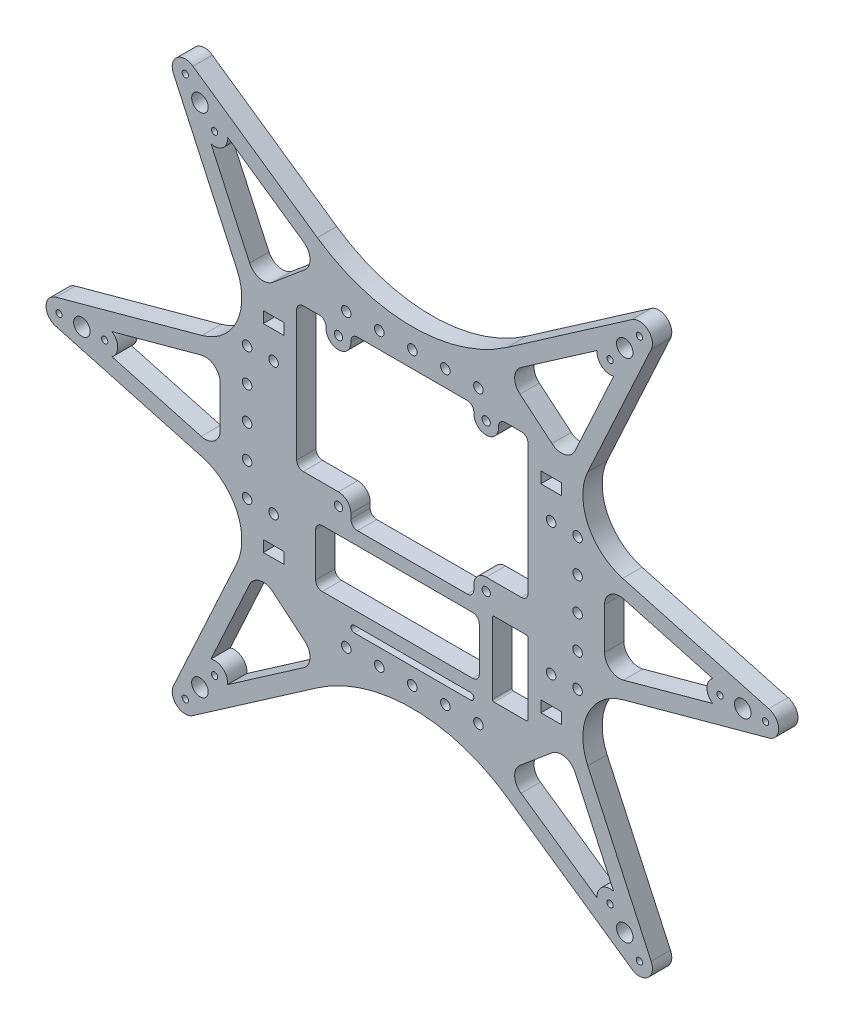
SolidWorks part; units mm, degrees
material "Acrylic (Medium-high impact)"
ref_plane "Front Plane" through (0, 0, 0) normal (0, 0, 1) x (1, 0, 0)
ref_plane "Top Plane" through (0, 0, 0) normal (0, 1, 0) x (1, 0, 0)
ref_plane "Right Plane" through (0, 0, 0) normal (1, 0, 0) x (0, 0, -1)
sketch "Sketch1" plane through (0, 0, 0) normal (0, 0, 1) x (1, 0, 0)
  line L0 (587.1768, 489.0962) -> (587.1768, 412.0041) construction
  line L1 (549.3782, 453.8298) -> (576.3894, 461.205)
  line L2 (582.1207, 456.8289) -> (582.1207, 444.2715)
  line L3 (595.1767, 418.8502) -> (601.3767, 422.2502) construction
  line L4 (595.1767, 422.2502) -> (601.3767, 418.8502) construction
  line L5 (568.9811, 379.8335) -> (581.557, 369.2811) construction
  line L6 (640.2767, 406.5502) -> (630.2767, 406.5502) construction
  line L7 (590.2767, 450.5502) -> (590.2767, 440.5502) construction
  line L8 (-358.708, 400.5502) -> (49641.292, 400.5502) construction
  line L9 (532.4267, 446.7161) -> (532.4267, 454.3842) construction
  line L10 (640.2767, 450.5502) -> (-31503.6634, -37857.1058) construction
  line L11 (704.5554, 373.9457) -> (708.9906, 368.66) construction
  line L12 (704.5554, 373.9457) -> (700.1202, 379.2314) construction
  line L13 (709.6013, 367.9323) -> (706.6642, 365.4678) construction
  line L14 (575.9979, 527.1546) -> (571.5627, 532.4403) construction
  line L15 (575.9979, 527.1546) -> (580.4331, 521.8689) construction
  line L16 (712.5384, 370.3968) -> (709.6013, 367.9323) construction
  line L17 (576.6167, 466.4501) -> (576.6167, 434.6502) construction
  line L18 (663.4579, 422.9239) -> (640.2767, 450.5502) construction
  line L19 (570.952, 533.1681) -> (573.8891, 535.6326) construction
  line L20 (568.0149, 370.3968) -> (570.952, 367.9323) construction
  line L21 (540.2767, 450.5502) -> (547.1767, 450.5502) construction
  line L22 (-351.1587, 450.5502) -> (49648.8413, 450.5502) construction
  line L23 (685.3767, 422.2502) -> (679.1767, 418.8502) construction
  line L24 (685.3767, 418.8502) -> (679.1767, 422.2502) construction
  line L25 (685.3767, 482.2502) -> (679.1767, 478.8502) construction
  line L26 (587.1768, 489.0962) -> (568.0149, 530.7036)
  line L27 (570.952, 367.9323) -> (573.8891, 365.4678) construction
  line L28 (575.9979, 373.9457) -> (580.4331, 379.2314) construction
  line L29 (685.3767, 478.8502) -> (679.1767, 482.2502) construction
  line L30 (611.5369, 509.5368) -> (573.8891, 535.6326)
  line L31 (568.0149, 530.7036) -> (570.952, 533.1681) construction
  line L32 (610.8062, 450.5502) -> (605.2767, 450.5502) construction
  line L33 (605.2767, 489.5502) -> (675.2767, 489.5502)
  line L34 (663.4579, 478.1765) -> (640.2767, 450.5502) construction
  line L35 (540.2767, 450.5502) -> (533.3767, 450.5502) construction
  line L36 (576.6167, 466.4501) -> (532.4267, 454.3842)
  line L37 (575.9979, 373.9457) -> (571.5627, 368.66) construction
  line L38 (595.1767, 422.2502) -> (595.1767, 418.8502)
  line L39 (595.1767, 422.2502) -> (601.3767, 422.2502)
  line L40 (601.3767, 422.2502) -> (601.3767, 418.8502)
  line L41 (640.2767, 450.5502) -> (675.2767, 450.5502) construction
  line L42 (595.1767, 418.8502) -> (601.3767, 418.8502)
  line L43 (731.1751, 447.2706) -> (704.1639, 439.8953)
  line L44 (685.3767, 418.8502) -> (679.1767, 418.8502)
  line L45 (740.2767, 450.5502) -> (747.1767, 450.5502) construction
  line L46 (693.3765, 412.0041) -> (712.5384, 370.3968)
  line L47 (669.7471, 450.5502) -> (675.2767, 450.5502) construction
  line L48 (669.0164, 391.5635) -> (706.6642, 365.4678)
  line L49 (703.9366, 434.6502) -> (748.1267, 446.7161)
  line L50 (712.5384, 530.7036) -> (709.6013, 533.1681) construction
  line L51 (740.2767, 450.5502) -> (733.3767, 450.5502) construction
  line L52 (701.2173, 383.026) -> (689.5047, 408.4585)
  line L53 (696.1927, 378.8099) -> (673.1805, 394.7609)
  line L54 (709.6013, 533.1681) -> (706.6642, 535.6326) construction
  line L55 (672.8516, 401.9043) -> (682.5269, 410.0229)
  line L56 (703.9366, 466.4501) -> (703.9366, 434.6502) construction
  line L57 (679.1767, 422.2502) -> (679.1767, 418.8502)
  line L58 (704.5554, 527.1546) -> (700.1202, 521.8689) construction
  line L59 (704.5554, 527.1546) -> (708.9906, 532.4403) construction
  line L60 (748.1267, 446.7161) -> (748.1267, 454.3842) construction
  line L61 (685.3767, 422.2502) -> (679.1767, 422.2502)
  line L62 (1630.6528, 450.5502) -> (-48369.3472, 450.5502) construction
  line L63 (691.7267, 450.5502) -> (588.8267, 450.5502) construction
  line L64 (607.7017, 401.9043) -> (598.0264, 410.0229)
  line L65 (640.2767, 450.5502) -> (-31503.6634, 38758.2062) construction
  line L66 (584.3606, 378.8099) -> (607.3728, 394.7609)
  line L67 (693.3765, 489.0962) -> (693.3765, 412.0041) construction
  line L68 (-358.708, 500.5502) -> (49641.292, 500.5502) construction
  line L69 (579.336, 518.0744) -> (591.0486, 492.6418)
  line L70 (685.3767, 422.2502) -> (685.3767, 418.8502)
  line L71 (685.3767, 478.8502) -> (685.3767, 482.2502)
  line L72 (605.2767, 489.5502) -> (605.2767, 411.5502)
  line L73 (584.3606, 522.2905) -> (607.3728, 506.3395)
  line L74 (607.7017, 499.196) -> (598.0264, 491.0775)
  line L75 (685.3767, 478.8502) -> (679.1767, 478.8502)
  line L76 (679.1767, 478.8502) -> (679.1767, 482.2502)
  line L77 (672.8516, 499.196) -> (682.5269, 491.0775)
  line L78 (696.1927, 522.2905) -> (673.1805, 506.3395)
  line L79 (675.2767, 489.5502) -> (675.2767, 411.5502)
  line L80 (579.336, 383.026) -> (591.0486, 408.4585)
  line L81 (701.2173, 518.0744) -> (689.5047, 492.6418)
  line L82 (576.6167, 434.6502) -> (532.4267, 446.7161)
  line L83 (605.2767, 411.5502) -> (675.2767, 411.5502)
  line L84 (611.5369, 391.5635) -> (573.8891, 365.4678)
  line L85 (587.1768, 412.0041) -> (568.0149, 370.3968)
  line L86 (549.3782, 447.2706) -> (576.3894, 439.8953)
  line L87 (703.9366, 466.4501) -> (748.1267, 454.3842)
  line L88 (669.0164, 509.5368) -> (706.6642, 535.6326)
  line L89 (693.3765, 489.0962) -> (712.5384, 530.7036)
  line L90 (698.4326, 456.8289) -> (698.4326, 444.2715)
  line L91 (685.3767, 482.2502) -> (679.1767, 482.2502)
  line L97 (731.1751, 453.8298) -> (704.1639, 461.205)
  line L100 (590.2767, 450.5502) -> (590.2767, 460.5502) construction
  line L102 (640.2767, 494.5502) -> (630.2767, 494.5502) construction
  line L104 (568.9811, 521.2669) -> (581.557, 531.8192) construction
  line L111 (640.2767, -48598.7836) -> (640.2767, 49499.884) construction
  line L157 (595.1767, 482.2502) -> (601.3767, 482.2502)
  line L158 (601.3767, 478.8502) -> (601.3767, 482.2502)
  line L159 (595.1767, 478.8502) -> (601.3767, 482.2502) construction
  line L162 (595.1767, 482.2502) -> (601.3767, 478.8502) construction
  line L163 (595.1767, 478.8502) -> (601.3767, 478.8502)
  line L164 (595.1767, 478.8502) -> (595.1767, 482.2502)
  circle A0 centre (533.3767, 450.5502) radius 0.95
  circle A1 centre (598.2767, 430.5502) radius 1.45
  circle A2 centre (575.9979, 527.1546) radius 2.5
  circle A3 centre (547.1767, 450.5502) radius 0.95
  arc A4 (549.3782, 447.2706) -> (549.3782, 453.8298) centre (547.1767, 450.5502) ccw
  circle A5 centre (540.2767, 450.5502) radius 2.5
  arc A6 (532.4267, 446.7161) -> (532.4267, 454.3842) centre (533.3767, 450.5502) cw
  circle A7 centre (590.2767, 460.5502) radius 1.45
  circle A8 centre (571.5627, 532.4403) radius 0.95
  circle A9 centre (580.4331, 521.8689) radius 0.95
  arc A10 (579.336, 518.0744) -> (584.3606, 522.2905) centre (580.4331, 521.8689) ccw
  arc A11 (582.1207, 456.8289) -> (576.3894, 461.205) centre (577.5843, 456.8289) ccw
  circle A12 centre (690.2767, 440.5502) radius 1.45
  circle A13 centre (682.2767, 470.5502) radius 1.45
  circle A14 centre (640.2767, 406.5502) radius 1.45
  arc A15 (568.0149, 530.7036) -> (573.8891, 535.6326) centre (571.5627, 532.4403) cw
  circle A16 centre (690.2767, 430.5502) radius 1.45
  circle A17 centre (704.5554, 373.9457) radius 2.5
  circle A18 centre (708.9906, 368.66) radius 0.95
  circle A19 centre (700.1202, 379.2314) radius 0.95
  circle A20 centre (630.2767, 494.5502) radius 1.45
  circle A21 centre (620.2767, 494.5502) radius 1.45
  arc A22 (701.2173, 383.026) -> (696.1927, 378.8099) centre (700.1202, 379.2314) ccw
  arc A23 (698.4326, 444.2715) -> (704.1639, 439.8953) centre (702.969, 444.2715) ccw
  arc A24 (712.5384, 370.3968) -> (706.6642, 365.4678) centre (708.9906, 368.66) cw
  circle A25 centre (650.2767, 406.5502) radius 1.45
  circle A26 centre (660.2767, 406.5502) radius 1.45
  circle A27 centre (590.2767, 430.5502) radius 1.45
  arc A28 (682.5269, 410.0229) -> (689.5047, 408.4585) centre (685.4185, 406.5767) cw
  arc A29 (672.8516, 401.9043) -> (673.1805, 394.7609) centre (675.7432, 398.4582) ccw
  arc A30 (703.9366, 434.6502) -> (693.3765, 412.0041) centre (708.2497, 418.8538) ccw
  arc A31 (611.5369, 509.5368) -> (669.0164, 509.5368) centre (640.2767, 550.9991) ccw
  arc A34 (576.6167, 434.6502) -> (587.1768, 412.0041) centre (572.3036, 418.8538) cw
  arc A35 (607.7017, 401.9043) -> (607.3728, 394.7609) centre (604.8101, 398.4582) cw
  arc A36 (598.0264, 491.0775) -> (591.0486, 492.6418) centre (595.1348, 494.5236) cw
  arc A37 (607.7017, 499.196) -> (607.3728, 506.3395) centre (604.8101, 502.6422) ccw
  arc A38 (576.6167, 466.4501) -> (587.1768, 489.0962) centre (572.3036, 482.2466) ccw
  arc A39 (598.0264, 410.0229) -> (591.0486, 408.4585) centre (595.1348, 406.5767) ccw
  arc A40 (611.5369, 391.5635) -> (669.0164, 391.5635) centre (640.2767, 350.1012) cw
  circle A41 centre (620.2767, 406.5502) radius 1.45
  circle A42 centre (630.2767, 406.5502) radius 1.45
  arc A43 (568.0149, 370.3968) -> (573.8891, 365.4678) centre (571.5627, 368.66) ccw
  arc A44 (703.9366, 466.4501) -> (693.3765, 489.0962) centre (708.2497, 482.2466) cw
  arc A45 (672.8516, 499.196) -> (673.1805, 506.3395) centre (675.7432, 502.6422) cw
  arc A46 (682.5269, 491.0775) -> (689.5047, 492.6418) centre (685.4185, 494.5236) ccw
  circle A47 centre (682.2767, 430.5502) radius 1.45
  arc A48 (582.1207, 444.2715) -> (576.3894, 439.8953) centre (577.5843, 444.2715) cw
  circle A49 centre (590.2767, 470.5502) radius 1.45
  arc A50 (579.336, 383.026) -> (584.3606, 378.8099) centre (580.4331, 379.2314) cw
  circle A51 centre (580.4331, 379.2314) radius 0.95
  circle A52 centre (571.5627, 368.66) radius 0.95
  circle A53 centre (590.2767, 440.5502) radius 1.45
  circle A54 centre (575.9979, 373.9457) radius 2.5
  circle A58 centre (660.2767, 494.5502) radius 1.45
  circle A59 centre (650.2767, 494.5502) radius 1.45
  arc A63 (712.5384, 530.7036) -> (706.6642, 535.6326) centre (708.9906, 532.4403) ccw
  arc A66 (698.4326, 456.8289) -> (704.1639, 461.205) centre (702.969, 456.8289) cw
  arc A67 (701.2173, 518.0744) -> (696.1927, 522.2905) centre (700.1202, 521.8689) cw
  circle A68 centre (700.1202, 521.8689) radius 0.95
  circle A69 centre (708.9906, 532.4403) radius 0.95
  circle A70 centre (690.2767, 450.5502) radius 1.45
  arc A71 (748.1267, 446.7161) -> (748.1267, 454.3842) centre (747.1767, 450.5502) ccw
  circle A72 centre (740.2767, 450.5502) radius 2.5
  arc A74 (731.1751, 447.2706) -> (731.1751, 453.8298) centre (733.3767, 450.5502) cw
  circle A75 centre (733.3767, 450.5502) radius 0.95
  circle A76 centre (704.5554, 527.1546) radius 2.5
  circle A78 centre (747.1767, 450.5502) radius 0.95
  circle A81 centre (690.2767, 470.5502) radius 1.45
  circle A82 centre (640.2767, 494.5502) radius 1.45
  circle A86 centre (690.2767, 460.5502) radius 1.45
  circle A89 centre (590.2767, 450.5502) radius 1.45
  circle A129 centre (598.2767, 470.5502) radius 1.45
  circle A130 centre (590.2767, 480.5502) radius 1.45 [skipped]
  point P0 (640.2767, 500.5502)
  point P26 (698.4326, 450.5502)
  point P44 (582.1207, 450.5502)
  point P46 (582.1207, 450.5502)
  point P51 (598.2767, 420.5502)
  point P54 (602.8641, 495.1368)
  point P55 (582.9721, 518.843)
  point P64 (582.1207, 450.5502)
  point P74 (693.3765, 450.5502)
  point P82 (703.9366, 450.5502)
  point P97 (576.6167, 450.5502)
  point P104 (640.2767, 489.5502)
  point P110 (587.1768, 450.5502)
  point P124 (602.8641, 495.1368)
  point P191 (640.2767, 400.5502)
  point P192 (569.0236, 365.6342)
  point P199 (640.2767, 411.5502)
  point P200 (677.6892, 405.9636)
  point P201 (602.8641, 405.9636)
  point P202 (582.9721, 382.2573)
  point P229 (677.6892, 495.1368)
  point P231 (698.4326, 450.5502)
  point P238 (640.2767, 489.5502)
  point P242 (569.0236, 535.4662)
  point P307 (640.2767, 500.5502)
  point P366 (598.2767, 480.5502)
  dimension "D6" = 1.9
  dimension "D9" = 42
  dimension "D11" = 5
  dimension "D12" = 13.8
  dimension "D14" = 20
  dimension "D16" = 4
  dimension "D17" = 3
  dimension "D19" = 75
  dimension "D20" = 2.9
  dimension "D13" = 70
  dimension "D27" = 28
  dimension "D8" = 1.9
  dimension "D36" = 3
  dimension "D37" = 3
  dimension "D47" = 5
  dimension "D28" = 3
  dimension "D25" = 3
  dimension "D51" = 39
  dimension "D10" = 10
  dimension "D21" = 44
  dimension "D22" = 13.8
  dimension "D33" = 50
  dimension "D34" = 6.2
  dimension "D35" = 100
  dimension "D41" = 5
  dimension "D43" = 100
  dimension "D44" = 3.4
  dimension "D53" = 10
  dimension "D56" = 10
  dimension "D59" = 5
  dimension "D61" = 28
extrude "Boss-Extrude1" add sketch "Sketch1" along normal blind 5.85
sketch "Sketch2" plane through (0, 0, 5.85) normal (0, 0, 1) x (1, 0, 0)
  line L0 (605.2767, 489.5502) -> (605.2767, 411.5502) construction
  line L1 (675.2767, 411.5502) -> (675.2767, 489.5502) construction
  line L2 (605.2767, 411.5502) -> (675.2767, 411.5502) construction
  line L3 (675.2767, 489.5502) -> (605.2767, 489.5502)
  line L4 (605.2767, 446.1202) -> (605.2767, 411.5502)
  line L5 (617.9217, 487.0802) -> (617.9217, 442.3702) construction
  line L6 (605.2767, 411.5502) -> (621.6717, 411.5502)
  line L7 (529.4267, 450.5502) -> (751.1267, 450.5502) construction
  line L8 (640.2767, 400.5502) -> (640.2767, 500.5502) construction
  line L9 (662.6317, 487.0802) -> (662.6317, 442.3702) construction
  line L10 (617.9217, 487.0802) -> (662.6317, 487.0802) construction
  line L11 (662.6317, 446.1202) -> (675.2767, 446.1202)
  line L12 (658.8817, 489.5502) -> (666.3817, 489.5502)
  line L13 (658.8817, 487.0802) -> (658.8817, 489.5502)
  line L14 (621.6717, 487.0802) -> (621.6717, 489.5502)
  line L15 (621.6717, 489.5502) -> (614.1717, 489.5502)
  line L16 (614.1717, 487.0802) -> (614.1717, 489.5502)
  line L17 (621.0534, 485.0174) -> (614.1717, 489.5502) construction
  line L18 (621.6717, 489.5502) -> (614.7899, 485.0174) construction
  line L19 (659.4999, 485.0174) -> (666.3817, 489.5502) construction
  line L20 (658.8817, 489.5502) -> (665.7634, 485.0174) construction
  line L21 (666.3817, 487.0802) -> (666.3817, 489.5502)
  line L22 (621.6717, 411.5502) -> (621.6717, 413.5502)
  line L23 (617.9217, 446.1202) -> (605.2767, 446.1202)
  line L24 (658.8817, 411.5502) -> (658.8817, 413.5502)
  line L25 (621.6717, 438.8202) -> (658.8817, 438.8202)
  line L26 (658.8817, 411.5502) -> (675.2767, 411.5502)
  line L27 (675.2767, 411.5502) -> (675.2767, 414.5502)
  line L28 (621.6717, 442.3702) -> (621.6717, 438.8202)
  line L29 (658.8817, 442.3702) -> (658.8817, 438.8202)
  line L30 (658.8817, 413.5502) -> (621.6717, 413.5502)
  line L31 (664.5267, 437.0502) -> (675.2767, 437.0502)
  line L32 (664.5267, 414.5502) -> (675.2767, 414.5502)
  line L33 (611.0267, 434.8202) -> (660.5267, 434.8202)
  line L34 (660.5267, 434.8202) -> (660.5267, 417.5502)
  line L35 (664.5267, 437.0502) -> (664.5267, 414.5502)
  line L36 (660.5267, 417.5502) -> (611.0267, 417.5502)
  line L37 (675.2767, 414.5502) -> (675.2767, 437.0502)
  line L38 (611.0267, 417.5502) -> (611.0267, 434.8202)
  line L39 (611.0267, 434.8202) -> (611.0267, 417.5502)
  line L40 (675.2767, 437.0502) -> (675.2767, 446.1202)
  circle A0 centre (617.9217, 487.0802) radius 1.25
  circle A1 centre (662.6317, 487.0802) radius 1.25
  arc A2 (662.6317, 446.1202) -> (658.8817, 442.3702) centre (662.6317, 442.3702) ccw
  circle A3 centre (662.6317, 442.3702) radius 1.25
  arc A4 (621.6717, 487.0802) -> (614.1717, 487.0802) centre (617.9217, 487.0802) cw
  arc A5 (658.8817, 487.0802) -> (666.3817, 487.0802) centre (662.6317, 487.0802) ccw
  arc A6 (617.9217, 446.1202) -> (621.6717, 442.3702) centre (617.9217, 442.3702) cw
  circle A7 centre (617.9217, 442.3702) radius 1.25
  dimension "D1" = 2.47
  dimension "D2" = 3.75
  dimension "D3" = 44.71
  dimension "D4" = 4
  dimension "D8" = 44.71
  dimension "D5" = 4
  dimension "D6" = 2
  dimension "D7" = 4
extrude "Boss-Extrude3" add sketch "Sketch2" against normal up to surface (5.85 mm away) separate body contours A4 L14 L3 L16 A0 | L13 A5 L21 L3 A1 | A6 L23 L22 L30 L24 L32 L35 L31 L11 A2 L29 L25 L28 A3 L36 L38 L33 L34 A7 region at (666.2842, 488.3152, 5.85) region at (621.5742, 488.3152, 5.85) region at (611.5992, 445.3395, 5.85) up to face at (598.2767, 480.5502, 0)
combine bodies "Combine1" operation type add bodies to combine 118 119 120 114
fillet "Fillet2" radius 2 1 edges at (621.6717, 438.8202, 2.925)
fillet "Fillet3" radius 2 9 edges at (614.1717, 489.5502, 2.925) (658.8817, 489.5502, 2.925) (666.3817, 489.5502, 2.925) (621.6717, 489.5502, 2.925) (660.5267, 417.5502, 2.925) (611.0267, 417.5502, 2.925) (611.0267, 434.8202, 2.925) (660.5267, 434.8202, 2.925) (658.8817, 438.8202, 2.925)
fillet "Fillet4" radius 0.5 4 edges at (675.2767, 414.5502, 2.925) (664.5267, 414.5502, 2.925) (675.2767, 437.0502, 2.925) (664.5267, 437.0502, 2.925)
fillet "Fillet5" radius 1 4 edges at (658.8817, 411.5502, 2.925) (658.8817, 413.5502, 2.925) (621.6717, 411.5502, 2.925) (621.6717, 413.5502, 2.925)
fillet "Fillet6" radius 2 4 edges at (675.2767, 446.1202, 2.925) (675.2767, 489.5502, 2.925) (605.2767, 489.5502, 2.925) (605.2767, 446.1202, 2.925)
